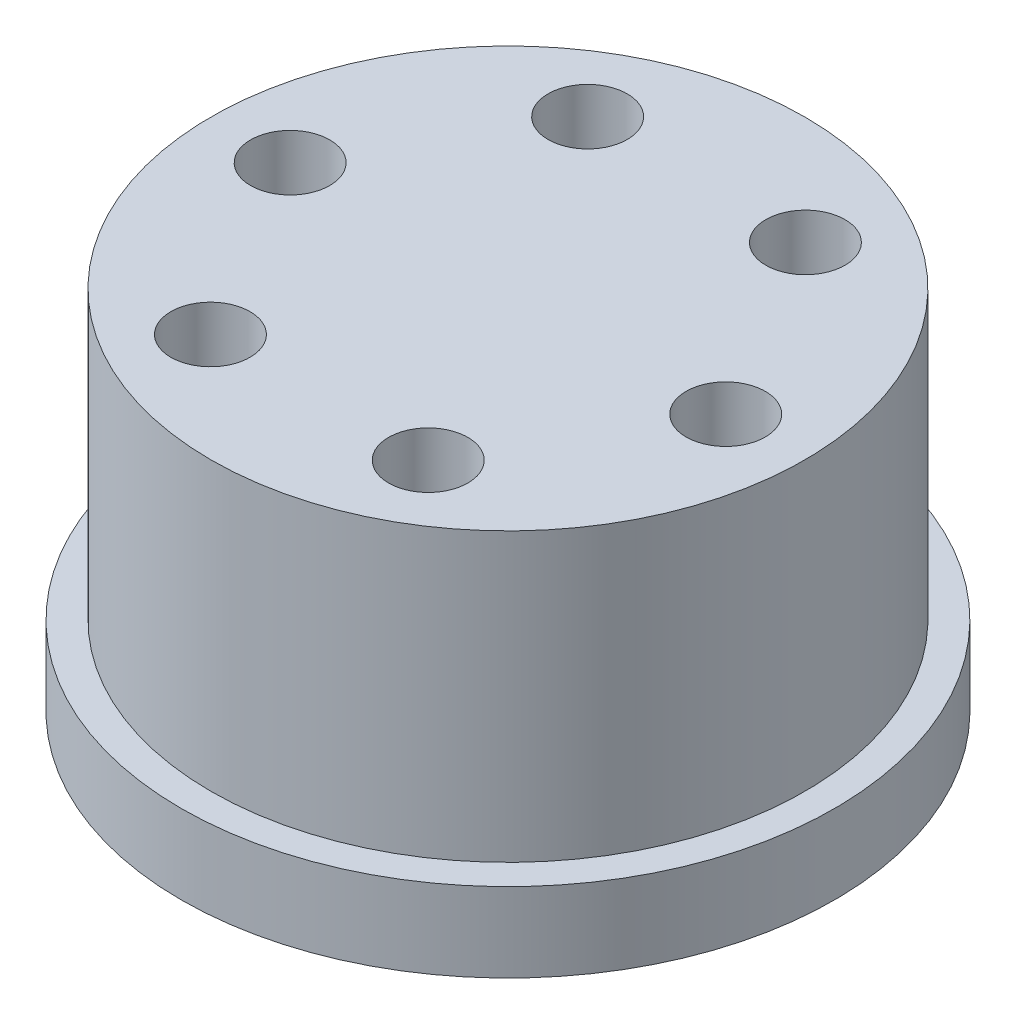
SolidWorks part; units mm, degrees
ref_plane "Front Plane" through (0, 0, 0) normal (0, 0, 1) x (1, 0, 0)
ref_plane "Top Plane" through (0, 0, 0) normal (0, 1, 0) x (1, 0, 0)
ref_plane "Right Plane" through (0, 0, 0) normal (1, 0, 0) x (0, 0, -1)
sketch "Sketch1" plane through (0, 0, 0) normal (0, 1, 0) x (1, 0, 0)
  circle A0 centre (0, 0) radius 16.5
  circle A1 centre (0, 0) radius 12.5 construction
  circle A2 centre (0, 12.5) radius 1.75
  circle A3 centre (10.8253, 6.25) radius 1.75
  circle A4 centre (10.8253, -6.25) radius 1.75
  circle A5 centre (0, -12.5) radius 1.75
  circle A6 centre (-10.8253, -6.25) radius 1.75
  circle A7 centre (-10.8253, 6.25) radius 1.75
  point P19 (0, 0)
  dimension "D1" = 33
  dimension "D2" = 25
  dimension "D3" = 3.5
  dimension "D4" = 6
extrude "Boss-Extrude1" add sketch "Sketch1" along normal blind 4
sketch "Sketch2" plane through (0, 4, 0) normal (0, 1, 0) x (1, 0, 0)
  circle A0 centre (0, 0) radius 15
  dimension "D1" = 30
extrude "Boss-Extrude2" add sketch "Sketch2" along normal blind 14.5
sketch "Sketch5" plane through (0, 18.5, 0) normal (0, 1, 0) x (1, 0, 0)
  circle A0 centre (0, 0) radius 11 construction
  circle A1 centre (-11, 0) radius 2
  circle A2 centre (-5.5, 9.5263) radius 2
  circle A3 centre (5.5, 9.5263) radius 2
  circle A4 centre (11, 0) radius 2
  circle A5 centre (5.5, -9.5263) radius 2
  circle A6 centre (-5.5, -9.5263) radius 2
  point P17 (0, 0)
  dimension "D1" = 22
  dimension "D2" = 4
  dimension "D3" = 6
extrude "Cut-Extrude3" cut sketch "Sketch5" against normal blind 6.5
sketch "Sketch6" plane through (0, 0, 0) normal (0, -1, 0) x (1, 0, 0)
  circle A0 centre (0, 0) radius 7.6
  dimension "D1" = 15.2
extrude "Cut-Extrude4" cut sketch "Sketch6" against normal blind 5
